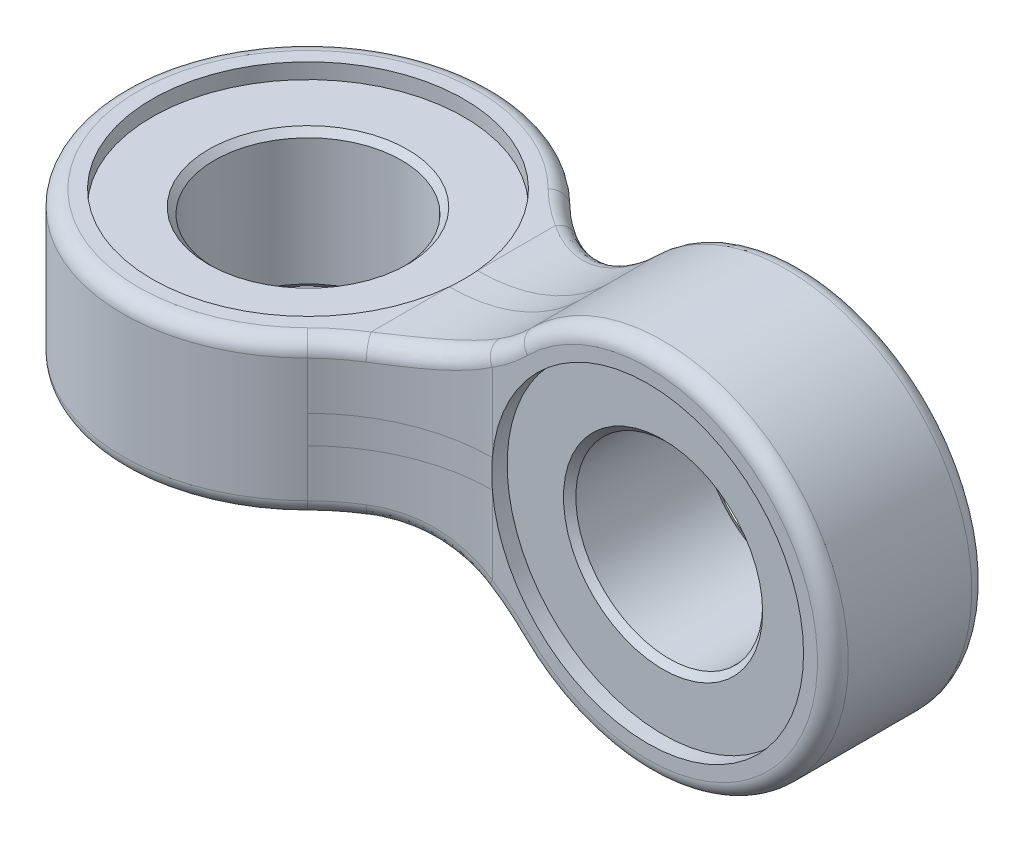
SolidWorks part; units mm, degrees
material "ABS"
ref_plane "Front Plane" through (0, 0, 0) normal (0, 0, 1) x (1, 0, 0)
ref_plane "Top Plane" through (0, 0, 0) normal (0, 1, 0) x (1, 0, 0)
ref_plane "Right Plane" through (0, 0, 0) normal (1, 0, 0) x (0, 0, -1)
sketch "Sketch1" plane through (0, 0, 0) normal (0, 1, 0) x (1, 0, 0)
  line L0 (0, 0) -> (21, 0) construction
  line L1 (21, -2.5) -> (21, 2.5)
  line L2 (21, 2.5) -> (5.4544, 2.5)
  line L3 (21, -2.5) -> (5.4544, -2.5)
  line L4 (0, 0) -> (-6, 0) construction
  line L5 (12, -2.5) -> (18, -2.5) construction
  line L6 (12, -2.5) -> (12, 2.5) construction
  line L7 (12, 2.5) -> (18, 2.5) construction
  line L8 (18, -2.5) -> (18, 2.5) construction
  line L9 (12, -2.5) -> (18, 2.5) construction
  line L10 (12, 2.5) -> (18, -2.5) construction
  circle A0 centre (0, 0) radius 3.025
  arc A1 (5.4544, 2.5) -> (5.4544, -2.5) centre (0, 0) ccw
  point P4 (15, 0)
  point P8 (21, 0)
  dimension "D1" = 6.05
  dimension "D2" = 6
  dimension "D3" = 15
  dimension "D4" = 6
  dimension "D5" = 5
  dimension "D6" = 6
extrude "Boss-Extrude1" add sketch "Sketch1" along normal blind 14.1
ref_plane "Plane1" through (0, 0, 0) normal (0, 0, -1) x (-1, 0, 0)
sketch "Sketch2" plane through (0, 0, 0) normal (0, 0, -1) x (-1, 0, 0)
  line L0 (-21, 7.05) -> (6, 7.05) construction
  line L1 (-21, 14.1) -> (-21, 0) construction
  line L2 (6, 0) -> (6, 14.1) construction
  line L4 (-6, 4.55) -> (6, 4.55)
  line L5 (-6, 4.55) -> (-6, 9.55) construction
  line L6 (-6, 9.55) -> (6, 9.55)
  line L7 (6, 4.55) -> (6, 9.55) construction
  line L8 (-6, 4.55) -> (6, 9.55) construction
  line L9 (-6, 9.55) -> (6, 4.55) construction
  line L10 (-6, 9.55) -> (-6, 14.1)
  line L11 (-6, 14.1) -> (6, 14.1)
  line L12 (6, 14.1) -> (6, 9.55)
  line L13 (6, 4.55) -> (6, 0)
  line L14 (6, 0) -> (-6, 0)
  line L15 (-6, 0) -> (-6, 4.55)
  point P6 (0, 7.05)
  dimension "D1" = 5
extrude "Cut-Extrude1" cut sketch "Sketch2" against normal through all both and the other way through all
sketch "Sketch3" plane through (0, 0, -2.5) normal (0, 0, -1) x (-1, 0, 0)
  line L0 (-21, 7.05) -> (-5.4544, 7.05) construction
  line L1 (-21, 14.1) -> (-21, 0) construction
  line L2 (-5.4544, 9.55) -> (-5.4544, 4.55) construction
  line L3 (-13.5, 14.1) -> (-13.5, 0) construction
  line L4 (-21, 14.1) -> (-6, 14.1) construction
  line L5 (-21, 0) -> (-6, 0) construction
  circle A0 centre (-13.5, 7.05) radius 3.025
  dimension "D1" = 6.05
extrude "Cut-Extrude2" cut sketch "Sketch3" against normal through all
sketch "Sketch4" plane through (0, 0, -2.5) normal (0, 0, -1) x (-1, 0, 0)
  line L0 (-6, 9.55) -> (-8.0456, 9.55)
  line L1 (-6, 4.55) -> (-8.0456, 4.55)
  line L2 (-6, 4.55) -> (-6, 0)
  line L3 (-6, 0) -> (-21, 0)
  line L4 (-21, 0) -> (-21, 14.1)
  line L5 (-21, 14.1) -> (-6, 14.1)
  line L6 (-6, 14.1) -> (-6, 9.55)
  line L7 (-21, 14.1) -> (-6, 14.1) construction
  line L8 (-21, 0) -> (-6, 0) construction
  line L9 (-21, 14.1) -> (-21, 0) construction
  arc A0 (-8.0456, 9.55) -> (-8.0456, 4.55) centre (-13.5, 7.05) ccw
  line M6 (-21, 0) -> (-6, 0)
  line M7 (-6, 0) -> (-6, 4.55)
  line M11 (-6, 9.55) -> (-6, 14.1)
  line M12 (-6, 14.1) -> (-21, 14.1)
  line M13 (-21, 14.1) -> (-21, 0)
  dimension "D1" = 6
extrude "Cut-Extrude3" cut sketch "Sketch4" against normal blind 10 contours A0 L3 L1 M7 | A0 L0 M11 M12 | A0 L5 M13 | A0 M13 M6 region at (7.0228, 9.7559, -2.5)
sketch "Sketch6" plane through (0, 9.55, 0) normal (0, 1, 0) x (1, 0, 0)
  circle A0 centre (0, 0) radius 5.05
  dimension "D1" = 10.1
extrude "Cut-Extrude4" cut sketch "Sketch6" against normal blind 0.5
sketch "Sketch7" plane through (0, 0, 2.5) normal (0, 0, 1) x (1, 0, 0)
  circle A0 centre (13.5, 7.05) radius 5.05
  dimension "D1" = 10.1
extrude "Cut-Extrude5" cut sketch "Sketch7" against normal blind 0.5
fillet "Fillet1" radius 6 4 edges at (5.4544, 7.05, 2.5) (8.0456, 4.55, 0) (5.4544, 7.05, -2.5) (8.0456, 9.55, 0)
chamfer "Chamfer1" distance 0.2 angle 45 4 edges at (10.475, 7.05, -2.5) (-3.025, 4.55, 0) (16.525, 7.05, 2) (0, 9.05, 3.025)
fillet "Fillet2" radius 0.5 16 edges at (6.3839, 9.7049, 2.8745) (19.5, 7.05, 2.5) (7.1161, 4.1755, 2.6549) (-6, 4.55, 0) (7.1161, 4.1755, -2.6549) (19.5, 7.05, -2.5) (6.3839, 9.7049, -2.8745) (-6, 9.55, 0) (4.618, 9.55, 3.9002) (4.618, 9.55, -3.9002) (8.882, 10.9502, 2.5) (8.882, 3.1498, 2.5) (4.618, 4.55, 3.9002) (4.618, 4.55, -3.9002) (8.882, 3.1498, -2.5) (8.882, 10.9502, -2.5)
